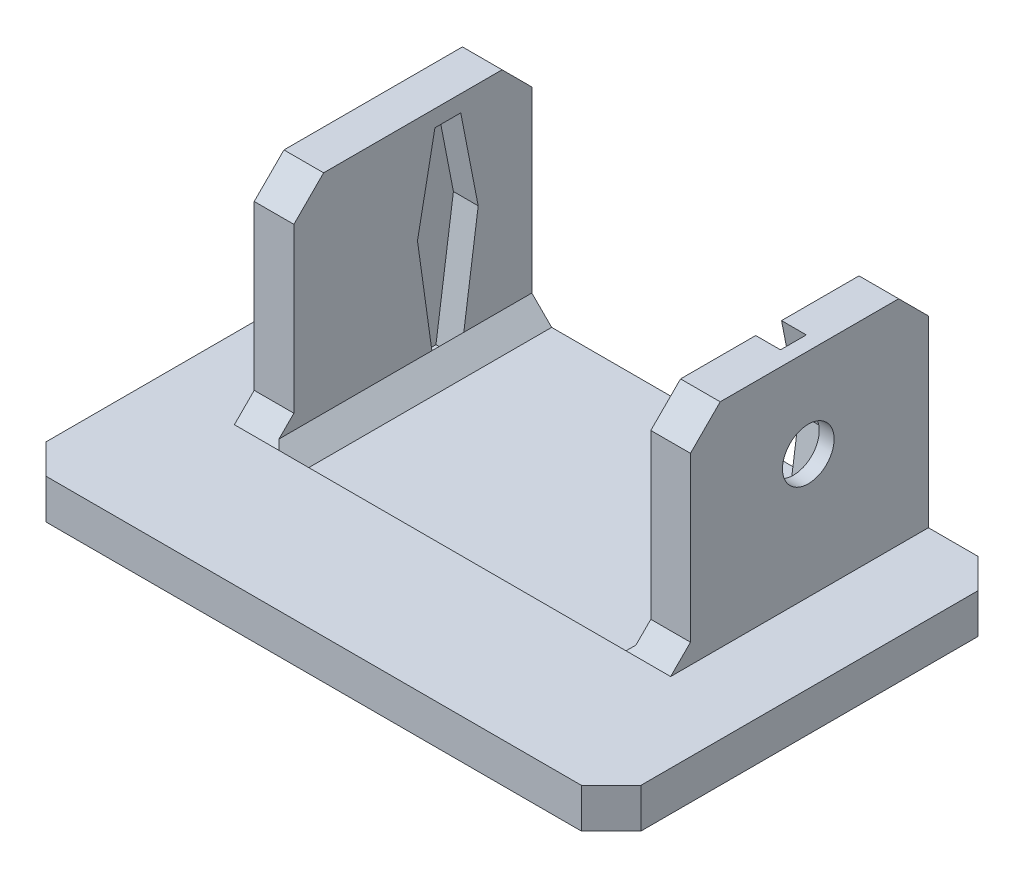
SolidWorks part; units mm, degrees
ref_plane "Front Plane" through (0, 0, 0) normal (0, 0, 1) x (1, 0, 0)
ref_plane "Top Plane" through (0, 0, 0) normal (0, 1, 0) x (1, 0, 0)
ref_plane "Right Plane" through (0, 0, 0) normal (1, 0, 0) x (0, 0, -1)
sketch "Sketch1" plane through (0, 0, 0) normal (0, 1, 0) x (1, 0, 0)
  line L1 (0, 0) -> (60, 0)
  line L2 (0, 0) -> (0, -40)
  line L3 (0, -40) -> (60, -40)
  line L4 (60, 0) -> (60, -40)
  dimension "D1" = 60
  dimension "D2" = 40
extrude "Boss-Extrude1" add sketch "Sketch1" along normal blind 4
chamfer "Chamfer1" distance 3 angle 45 4 edges at (0, 2, 40) (0, 2, 0) (60, 2, 0) (60, 2, 40)
sketch "Sketch2" plane through (0, 4, 0) normal (0, 1, 0) x (1, 0, 0)
  line L1 (12, 0) -> (48, 0)
  line L2 (12, 0) -> (12, -24)
  line L3 (12, -24) -> (48, -24)
  line L4 (48, 0) -> (48, -24)
  line L5 (60, -37) -> (60, -3) construction
  dimension "D1" = 36
  dimension "D2" = 24
  dimension "D3" = 12
extrude "Cut-Extrude1" cut sketch "Sketch2" against normal blind 1.5
sketch "Sketch3" plane through (0, 2.5, 0) normal (0, 1, 0) x (1, 0, 0)
  line L0 (30, 0) -> (30, 14.7408) construction
  line L1 (48, 0) -> (52, 0)
  line L2 (48, 0) -> (48, -24)
  line L3 (48, -24) -> (52, -24)
  line L4 (52, 0) -> (52, -24)
  line L5 (48, 0) -> (12, 0) construction
  line L6 (12, 0) -> (8, 0)
  line L7 (12, 0) -> (12, -24)
  line L8 (8, 0) -> (8, -24)
  line L9 (12, -24) -> (8, -24)
  dimension "D1" = 4
extrude "Boss-Extrude2" add sketch "Sketch3" along normal blind 23
chamfer "Chamfer2" distance 3 angle 45 4 edges at (10, 25.5, 0) (10, 25.5, 24) (50, 25.5, 0) (50, 25.5, 24)
chamfer "Chamfer3" distance 2 angle 45 2 edges at (50, 4, 24) (10, 4, 24)
chamfer "Chamfer4" distance 2 angle 45 1 edges at (30, 4, 24)
chamfer "Chamfer5" distance 2 angle 45 2 edges at (12, 2.5, 12.25) (48, 2.5, 12.25)
sketch "Sketch4" plane through (48, 0, 0) normal (-1, 0, 0) x (0, 0, 1)
  line L0 (3, 25.5) -> (21, 25.5) construction
  line L1 (9.0562, 16.5) -> (10.815, 25.5)
  line L5 (26, 4) -> (0, 4) construction
  line L7 (10.815, 4) -> (9.0562, 16.5)
  line L8 (12.1179, 16.5) -> (12.1179, -4.6484) construction
  line L9 (13.4207, 4) -> (15.1795, 16.5)
  line L10 (15.1795, 16.5) -> (13.4207, 25.5)
  line L11 (10.815, 4) -> (13.4207, 4)
  line L12 (10.815, 25.5) -> (13.4207, 25.5)
  dimension "D1" = 9
extrude "Cut-Extrude2" cut sketch "Sketch4" against normal blind 2.5
sketch "Sketch7" plane through (50.5, 0, 0) normal (-1, 0, 0) x (0, 0, 1)
  line L0 (12.1179, 25.5) -> (12.1179, 5.9876) construction
  line L1 (13.4207, 25.5) -> (10.815, 25.5) construction
  circle A0 centre (12.1179, 16.5) radius 2.604
  point P2 (12.1179, 15.1577)
  dimension "D1" = 9
extrude "Cut-Extrude3" cut sketch "Sketch7" against normal through all
sketch "Sketch8" plane through (12, 0, 0) normal (1, 0, 0) x (0, 0, -1)
  line L1 (-11.5326, 14.8219) -> (-9.7737, 23.8219)
  line L7 (-9.7737, 2.3219) -> (-11.5326, 14.8219)
  line L8 (-8.4709, 14.8219) -> (-8.4709, -6.3265) construction
  line L9 (-7.1681, 2.3219) -> (-5.4093, 14.8219)
  line L10 (-5.4093, 14.8219) -> (-7.1681, 23.8219)
  line L11 (-9.7737, 2.3219) -> (-7.1681, 2.3219)
  line L12 (-9.7737, 23.8219) -> (-7.1681, 23.8219)
extrude "Cut-Extrude4" cut sketch "Sketch8" against normal blind 2.5
